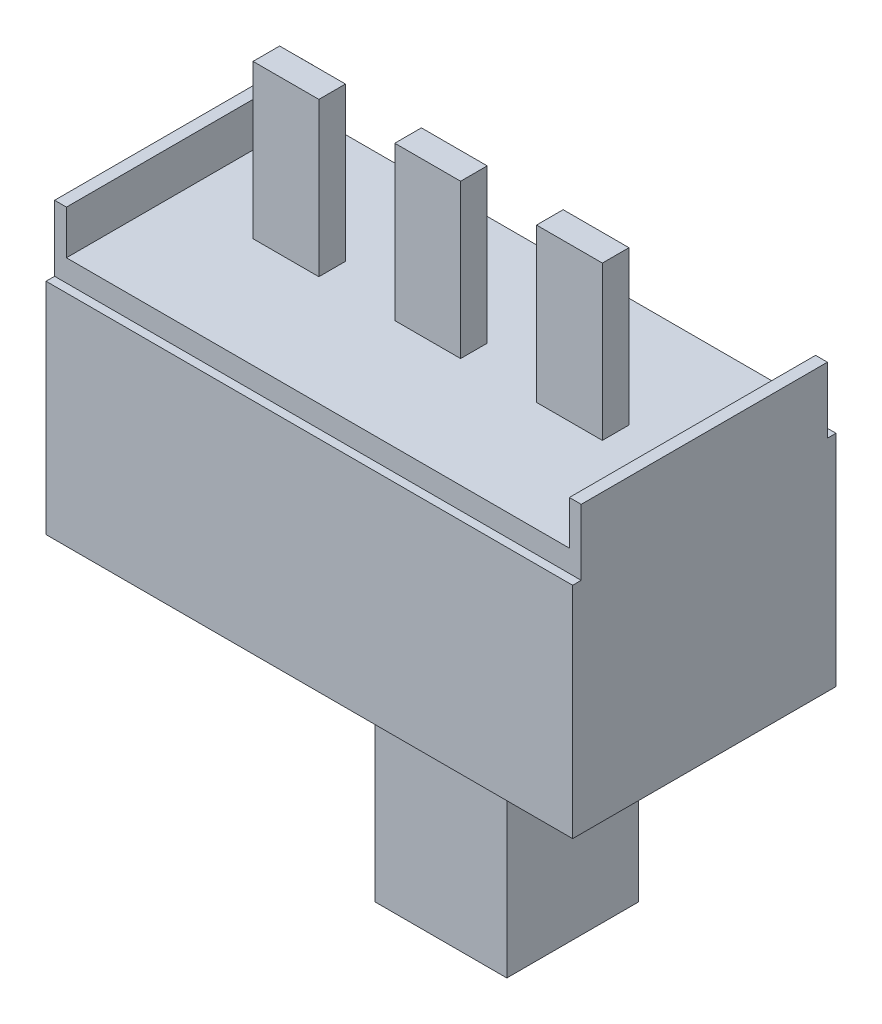
SolidWorks part; units mm, degrees
ref_plane "前视基准面" through (0, 0, 0) normal (0, 0, 1) x (1, 0, 0)
ref_plane "上视基准面" through (0, 0, 0) normal (0, 1, 0) x (1, 0, 0)
ref_plane "右视基准面" through (0, 0, 0) normal (1, 0, 0) x (0, 0, -1)
sketch "草图1" plane through (0, 0, 0) normal (0, 1, 0) x (1, 0, 0)
  line L1 (3, -1.5) -> (-3, -1.5)
  line L2 (3, -1.5) -> (3, 1.5)
  line L3 (3, 1.5) -> (-3, 1.5)
  line L4 (-3, -1.5) -> (-3, 1.5)
  line L5 (3, -1.5) -> (-3, 1.5) construction
  line L6 (3, 1.5) -> (-3, -1.5) construction
  line L7 (6, -3) -> (-6, -3)
  line L8 (6, -3) -> (6, 3)
  line L9 (6, 3) -> (-6, 3)
  line L10 (-6, -3) -> (-6, 3)
  line L11 (6, -3) -> (-6, 3) construction
  line L12 (6, 3) -> (-6, -3) construction
  point P0 (0, 0)
  point P6 (0, 0)
  dimension "D1" = 6
  dimension "D2" = 3
  dimension "D3" = 12
  dimension "D4" = 6
extrude "凸台-拉伸1" add sketch "草图1" along normal blind 5
sketch "草图2" plane through (0, 5, 0) normal (0, 1, 0) x (1, 0, 0)
  line L0 (5.73, 2.8051) -> (6, 2.8051)
  line L1 (5.73, -2.8051) -> (-5.73, -2.8051)
  line L2 (5.73, -2.8051) -> (5.73, 2.8051)
  line L3 (5.73, 2.8051) -> (-5.73, 2.8051)
  line L4 (-5.73, -2.8051) -> (-5.73, 2.8051)
  line L5 (5.73, -2.8051) -> (-5.73, 2.8051) construction
  line L6 (5.73, 2.8051) -> (-5.73, -2.8051) construction
  line L7 (6, -3) -> (6, 3) construction
  line L8 (6, 2.8051) -> (6, -2.8051)
  line L9 (6, -2.8051) -> (5.73, -2.8051)
  line L10 (-5.73, 2.8051) -> (-6, 2.8051)
  line L11 (-6, 3) -> (-6, -3) construction
  line L12 (-6, 2.8051) -> (-6, -2.8051)
  line L13 (-6, -2.8051) -> (-5.73, -2.8051)
  line L14 (-7.2152, 0) -> (8.9542, 0) construction
  line L15 (0, 12.8368) -> (0, -4.0232) construction
  line L16 (2.48, -0.3032) -> (3.98, -0.3032)
  line L17 (2.48, -0.3032) -> (2.48, 0.3032)
  line L18 (2.48, 0.3032) -> (3.98, 0.3032)
  line L19 (3.98, -0.3032) -> (3.98, 0.3032)
  line L20 (2.48, -0.3032) -> (3.98, 0.3032) construction
  line L21 (2.48, 0.3032) -> (3.98, -0.3032) construction
  line L22 (-0.75, -0.3032) -> (0.75, -0.3032)
  line L23 (-0.75, -0.3032) -> (-0.75, 0.3032)
  line L24 (-0.75, 0.3032) -> (0.75, 0.3032)
  line L25 (0.75, -0.3032) -> (0.75, 0.3032)
  line L26 (-0.75, -0.3032) -> (0.75, 0.3032) construction
  line L27 (-0.75, 0.3032) -> (0.75, -0.3032) construction
  line L28 (-2.48, -0.3032) -> (-3.98, -0.3032)
  line L29 (-2.48, -0.3032) -> (-2.48, 0.3032)
  line L30 (-2.48, 0.3032) -> (-3.98, 0.3032)
  line L31 (-3.98, -0.3032) -> (-3.98, 0.3032)
  point P0 (0, 0)
  point P16 (3.23, 0)
  point P21 (0, 0)
  point P26 (0, 0)
  point P29 (0, 4.4068)
  line M8 (-6, 3) -> (-6, -3)
  line M10 (6, -3) -> (6, 3)
  line M12 (3, -1.5) -> (-3, -1.5)
  line M13 (-3, -1.5) -> (-3, 1.5)
  line M14 (-3, 1.5) -> (3, 1.5)
  line M15 (3, 1.5) -> (3, -1.5)
  dimension "D1" = 2.5
  dimension "D2" = 1.5
  dimension "D3" = 1.5
extrude "凸台-拉伸2" add sketch "草图2" along normal blind 0.5 contours L4 L1 L2 L3 L28 L31 L30 L18 L19 L16 M13 M14 M15 M12 | L30 L29 L28 L16 L17 L18 L25 L22 L23 L24 M13 M12 M15 M14 region at (5.6024, 5, 0) region at (2.74, 5, 0.3703)
extrude "凸台-拉伸3" add sketch "草图2<3>" along normal blind 1.5 contours L13 L4 L10 M8 | L9 L0 L2 M10 region at (5.865, 5, 0) region at (-5.865, 5, 0)
sketch "草图2<3>" plane through (0, 5, 0) normal (0, 1, 0) x (1, 0, 0) same geometry as "草图2"
extrude "凸台-拉伸4" add sketch "草图2<4>" along normal blind 4 contours L16 L19 L18 M15 | L18 L17 L16 M15 | L22 L25 L24 L23 | L29 L30 L28 M13 | L31 L28 L30 M13 region at (2.74, 5, 0) region at (3.49, 5, 0) region at (0, 5, 0) region at (-2.74, 5, 0) region at (-3.49, 5, 0)
sketch "草图2<4>" plane through (0, 5, 0) normal (0, 1, 0) x (1, 0, 0) same geometry as "草图2"
sketch "草图4" plane through (0, 5, 0) normal (0, -1, 0) x (1, 0, 0)
  line L4 (3, 1.5) -> (-3, 1.5)
  line L5 (-3, 1.5) -> (-3, -1.5)
  line L6 (-3, -1.5) -> (3, -1.5)
  line L7 (3, -1.5) -> (3, 1.5)
  line L8 (3, 1.5) -> (-3, 1.5)
  line L9 (-3, 1.5) -> (-3, -1.5)
  line L10 (-3, -1.5) -> (3, -1.5)
  line L11 (3, -1.5) -> (3, 1.5)
  dimension "D1" = 0
extrude "凸台-拉伸5" add sketch "草图4" along normal blind 4.5
sketch "草图6" plane through (0, 0.5, 0) normal (0, -1, 0) x (1, 0, 0)
  line L0 (-3, -1.5) -> (3, -1.5) construction
  line L1 (3, 1.5) -> (0, 1.5)
  line L2 (3, 1.5) -> (3, -1.5)
  line L3 (3, -1.5) -> (0, -1.5)
  line L4 (0, 1.5) -> (0, -1.5)
extrude "凸台-拉伸6" add sketch "草图6" along normal blind 5.5
